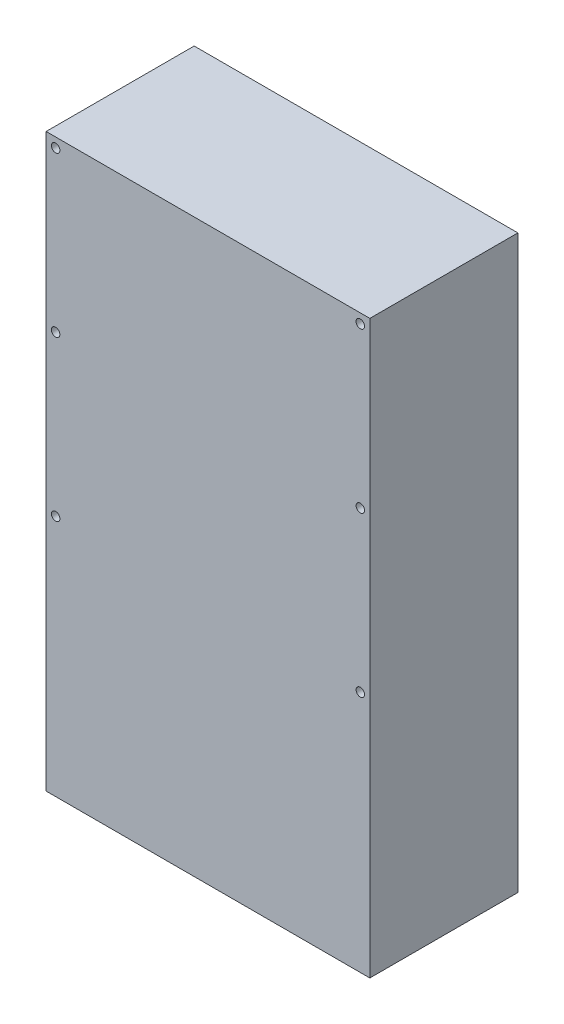
SolidWorks part; units mm, degrees
ref_plane "Front Plane" through (0, 0, 0) normal (0, 0, 1) x (1, 0, 0)
ref_plane "Top Plane" through (0, 0, 0) normal (0, 1, 0) x (1, 0, 0)
ref_plane "Right Plane" through (0, 0, 0) normal (1, 0, 0) x (0, 0, -1)
sketch "Sketch1" plane through (0, 0, 0) normal (0, 0, 1) x (1, 0, 0)
  line L0 (0, 50.8) -> (0, -381) construction
  line L1 (43.18, -65.2281) -> (-43.18, -65.2281)
  line L2 (43.18, -65.2281) -> (43.18, -217.6281)
  line L3 (43.18, -217.6281) -> (-43.18, -217.6281)
  line L4 (0, -65.2281) -> (0, -76.704) construction
  line L5 (-43.18, -65.2281) -> (-43.18, -217.6281)
  circle A0 centre (40.64, -67.7681) radius 1.1303 construction
  circle A1 centre (40.64, -110.3131) radius 1.1303 construction
  circle A2 centre (40.64, -152.8581) radius 1.1303 construction
  circle A3 centre (40.64, -67.7681) radius 1.1303
  circle A4 centre (40.64, -110.3131) radius 1.1303
  circle A5 centre (40.64, -152.8581) radius 1.1303
  circle A6 centre (-40.64, -152.8581) radius 1.1303
  circle A7 centre (-40.64, -110.3131) radius 1.1303
  circle A8 centre (-40.64, -67.7681) radius 1.1303
  point P26 (0, -217.6281)
  dimension "D1" = 2.54
  dimension "D2" = 2.54
  dimension "D3" = 152.4
extrude "Boss-Extrude1" add sketch "Sketch1" along normal offset from surface (39.497 mm away) 5.08
